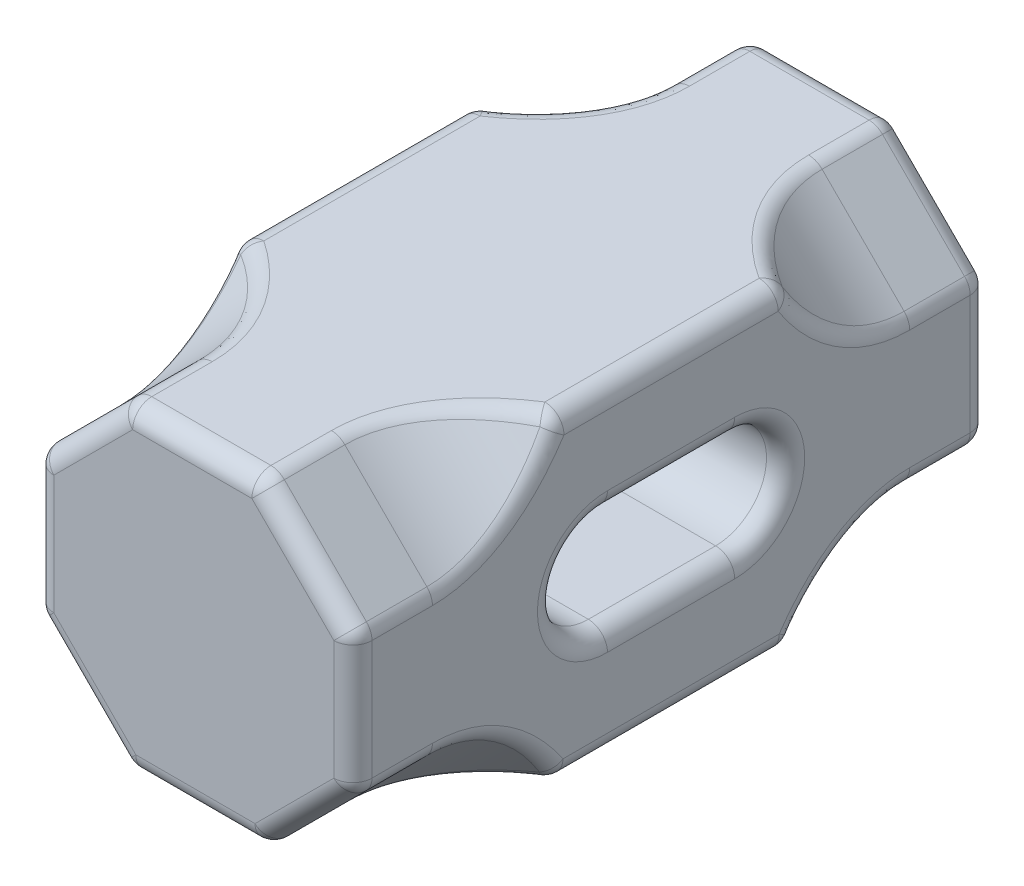
SolidWorks part; units mm, degrees
material "Gray Cast Iron"
ref_plane "Front Plane" through (0, 0, 0) normal (0, 0, 1) x (1, 0, 0)
ref_plane "Top Plane" through (0, 0, 0) normal (0, 1, 0) x (1, 0, 0)
ref_plane "Right Plane" through (0, 0, 0) normal (1, 0, 0) x (0, 0, -1)
sketch "Sketch1" plane through (0, 0, 0) normal (1, 0, 0) x (0, 0, -1)
  line L0 (-10, 0) -> (10, 0) construction
  line L1 (50, 25) -> (-50, 25)
  line L2 (50, 25) -> (50, -25)
  line L3 (50, -25) -> (-50, -25)
  line L4 (-50, 25) -> (-50, -25)
  line L5 (50, 25) -> (-50, -25) construction
  line L6 (50, -25) -> (-50, 25) construction
  line L7 (-10, 8) -> (10, 8)
  line L8 (-10, -8) -> (10, -8)
  arc A0 (-10, 8) -> (-10, -8) centre (-10, 0) ccw
  arc A1 (10, -8) -> (10, 8) centre (10, 0) ccw
  point P0 (0, 0)
  point P8 (0, 0)
  dimension "D4" = 8
  dimension "D1" = 100
  dimension "D2" = 50
  dimension "D3" = 20
extrude "Boss-Extrude1" add sketch "Sketch1" against normal mid plane 50
ref_plane "Plane1" through (0, 0, 0) normal (0.7071, -0.7071, 0) x (-0.7071, -0.7071, 0)
sketch "Sketch2" plane through (0, 0, 0) normal (0.7071, -0.7071, 0) x (-0.7071, -0.7071, 0)
  line L0 (-35.3553, 50) -> (-25, 50)
  line L1 (0, 50) -> (-35.3553, 50) construction
  line L2 (-25, 50) -> (-25, 37.5)
  line L3 (-35.3553, 17.2384) -> (-35.3553, 50)
  line L4 (0, 63.788) -> (0, -52.0633) construction
  line L5 (-32.6247, 0) -> (24.1773, 0) construction
  line L6 (35.3553, 17.2384) -> (35.3553, 50)
  line L7 (25, 50) -> (25, 37.5)
  line L8 (35.3553, 50) -> (25, 50)
  line L9 (35.3553, -50) -> (25, -50)
  line L10 (25, -50) -> (25, -37.5)
  line L11 (35.3553, -17.2384) -> (35.3553, -50)
  line L12 (-35.3553, -17.2384) -> (-35.3553, -50)
  line L13 (-25, -50) -> (-25, -37.5)
  line L14 (-35.3553, -50) -> (-25, -50)
  arc A0 (-25, 37.5) -> (-35.3553, 17.2384) centre (-50, 37.5) cw
  arc A1 (25, 37.5) -> (35.3553, 17.2384) centre (50, 37.5) ccw
  arc A2 (25, -37.5) -> (35.3553, -17.2384) centre (50, -37.5) cw
  arc A3 (-25, -37.5) -> (-35.3553, -17.2384) centre (-50, -37.5) ccw
  dimension "D2" = 50
  dimension "D3" = 25
  dimension "D1" = 12.5
extrude "Cut-Extrude1" cut sketch "Sketch2" against normal through all both and the other way through all
ref_plane "Plane2" through (0, 0, 0) normal (0.7071, 0.7071, 0) x (0.7071, -0.7071, 0)
sketch "Sketch3" plane through (0, 0, 0) normal (0.7071, 0.7071, 0) x (0.7071, -0.7071, 0)
  line L0 (-35.3553, 50) -> (-25.3553, 50)
  line L1 (-35.3553, 50) -> (-10.3553, 50) construction
  line L2 (-25.3553, 50) -> (-25.3553, 37.5)
  line L3 (-35.3553, 50) -> (-35.3553, -50) construction
  line L4 (-35.3553, 17.3108) -> (-35.3553, 50)
  line L5 (0, 50) -> (0, -16.2708) construction
  line L6 (-10.3553, 50) -> (10.3553, 50) construction
  line L7 (0, -39.5131) -> (0, 39.5131) construction
  line L8 (35.3553, 17.3108) -> (35.3553, 50)
  line L9 (25.3553, 50) -> (25.3553, 37.5)
  line L10 (35.3553, 50) -> (25.3553, 50)
  line L11 (-35.3553, 0) -> (35.3553, 0) construction
  line L12 (35.3553, -50) -> (35.3553, 50) construction
  line L13 (35.3553, -50) -> (25.3553, -50)
  line L14 (25.3553, -50) -> (25.3553, -37.5)
  line L15 (35.3553, -17.3108) -> (35.3553, -50)
  line L16 (-35.3553, -17.3108) -> (-35.3553, -50)
  line L17 (-25.3553, -50) -> (-25.3553, -37.5)
  line L18 (-35.3553, -50) -> (-25.3553, -50)
  arc A0 (-25.3553, 37.5) -> (-35.3553, 17.3108) centre (-50.7354, 37.5) cw
  arc A1 (25.3553, 37.5) -> (35.3553, 17.3108) centre (50.7354, 37.5) ccw
  arc A2 (25.3553, -37.5) -> (35.3553, -17.3108) centre (50.7354, -37.5) cw
  arc A3 (-25.3553, -37.5) -> (-35.3553, -17.3108) centre (-50.7354, -37.5) ccw
  dimension "D3" = 25.3801
  dimension "D1" = 10
  dimension "D2" = 12.5
extrude "Cut-Extrude2" cut sketch "Sketch3" against normal through all both and the other way through all
fillet "Fillet1" radius 3 60 edges at (17.6777, 17.6777, -50) (-17.9289, 17.9289, -50) (-17.6777, -17.6777, -50) (17.9289, -17.9289, -50) (-17.6777, -17.6777, 50) (-17.9289, 17.9289, 50) (17.6777, 17.6777, 50) (17.9289, -17.9289, 50) (-14.5871, 25, -26.235) (-10.8579, 25, -43.75) (-0.2513, 25, -50) (10.3553, 25, -43.75) (14.2287, 25, -26.1228) (14.2287, 25, 26.1228) (10.3553, 25, 43.75) (-0.2513, 25, 50) (-10.8579, 25, 43.75) (-14.5871, 25, 26.235) (25, -14.5871, 26.235) (25, -10.8579, 43.75) (25, -0.2513, 50) (25, 10.3553, 43.75) (25, 14.2287, 26.1228) (25, 25, 0) (25, 14.2287, -26.1228) (25, 10.3553, -43.75) (25, -0.2513, -50) (25, -10.8579, -43.75) (25, -14.5871, -26.235) (25, 0, -18) (25, 8, 0) (25, 0, 18) (25, -8, 0) (10.8579, -25, -43.75) (0.2513, -25, -50) (-10.3553, -25, -43.75) (-14.2287, -25, -26.1228) (-14.2287, -25, 26.1228) (-10.3553, -25, 43.75) (0.2513, -25, 50) (10.8579, -25, 43.75) (14.5871, -25, 26.235) (25, -25, 0) (14.5871, -25, -26.235) (-25, 8, 0) (-25, 0, -18) (-25, -8, 0) (-25, 0, 18) (-25, 10.8579, 43.75) (-25, 0.2513, 50) (-25, -10.3553, 43.75) (-25, -14.2287, 26.1228) (-25, -25, 0) (-25, -14.2287, -26.1228) (-25, -10.3553, -43.75) (-25, 0.2513, -50) (-25, 10.8579, -43.75) (-25, 14.5871, -26.235) (-25, 25, 0) (-25, 14.5871, 26.235)
equation "\"A\"= 50mm"
equation "\"D1@Boss-Extrude1\"=\"A\""
equation "\"D2@Sketch1\"=\"A\""
equation "\"D1@Sketch1\"=\"A\"*2"
equation "\"D1@Sketch2\"=\"A\"/4"
equation "\"D1@Sketch3\"=\"A\"*.2"
equation "\"D2@Sketch3\"=\"A\"*.25"
